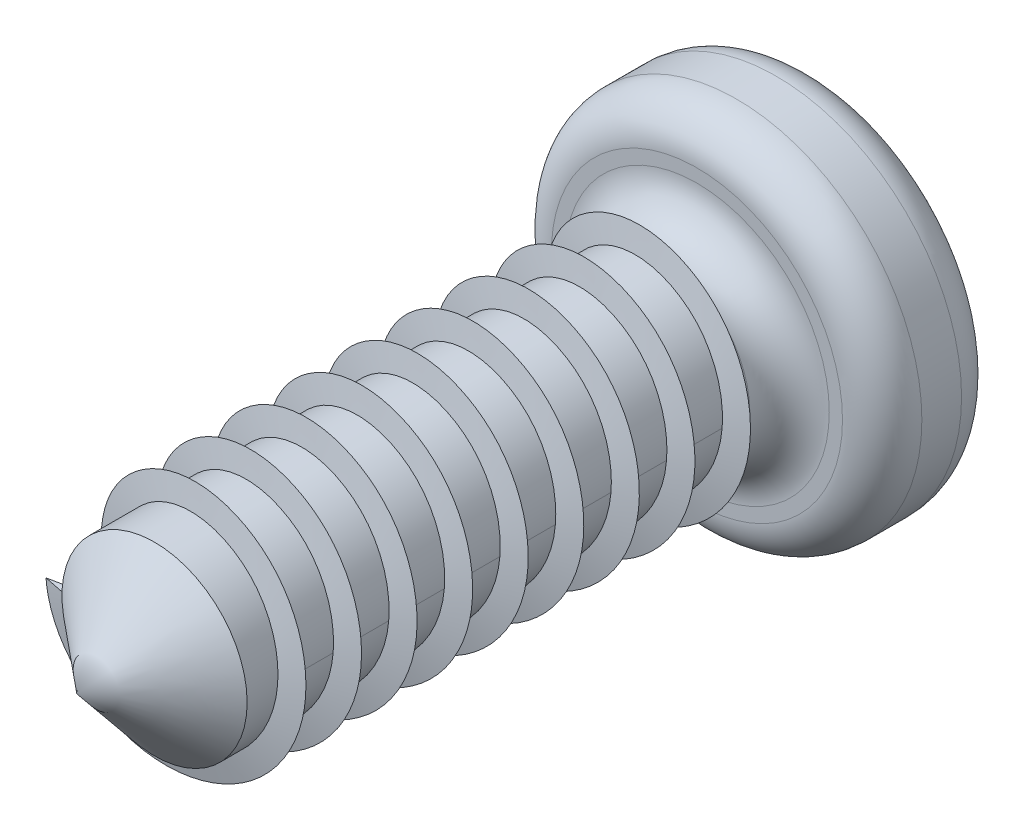
SolidWorks part; units mm, degrees
ref_plane "Front" through (0, 0, 0) normal (0, 0, 1) x (1, 0, 0)
ref_plane "Top" through (0, 0, 0) normal (0, 1, 0) x (1, 0, 0)
ref_plane "Right" through (0, 0, 0) normal (1, 0, 0) x (0, 0, -1)
sketch "Sketch1" plane through (0, 0, 0) normal (0, 0, 1) x (1, 0, 0)
  circle A0 centre (0, 0) radius 1.4
  dimension "D1" = 2.8
extrude "Boss-Extrude1" add sketch "Sketch1" along normal blind 5
sketch "Sketch2" plane through (0, 0, 5) normal (0, 0, 1) x (1, 0, 0)
  circle A0 centre (0, 0) radius 1.4 construction
  circle A1 centre (0, 0) radius 1.4
  circle A2 centre (0, 0) radius 0.7
  dimension "D1" = 0.7
extrude "Cut-Extrude1" cut sketch "Sketch2" against normal blind 4.1
sketch "Sketch3" plane through (0, 0, 5) normal (0, 0, 1) x (1, 0, 0)
  circle A0 centre (0, 0) radius 0.7
extrude "Boss-Extrude2" add sketch "Sketch3" along normal blind 0.6 draft 50
fillet "Fillet1" radius 0.3 2 edges at (1.4, 0, 0.9) (1.4, 0, 0)
fillet "Fillet2" radius 0.3 1 edges at (0.7, 0, 0.9)
sketch "Sketch4" plane through (0, 0, 0) normal (0, 0, -1) x (-1, 0, 0)
  line L0 (-0.15, -0.15) -> (-0.15, -0.9)
  line L1 (-0.15, 0.9) -> (0.15, 0.9)
  line L2 (-0.15, 0.9) -> (-0.15, 0.15)
  line L3 (-0.15, -0.9) -> (0.15, -0.9)
  line L4 (0.15, 0.9) -> (0.15, 0.15)
  line L5 (-0.15, 0.9) -> (0.15, -0.9) construction
  line L6 (-0.15, -0.9) -> (0.15, 0.9) construction
  line L7 (-0.9, -0.15) -> (-0.15, -0.15)
  line L8 (-0.9, -0.15) -> (-0.9, 0.15)
  line L9 (-0.9, 0.15) -> (-0.15, 0.15)
  line L10 (0.9, -0.15) -> (0.9, 0.15)
  line L11 (-0.9, -0.15) -> (0.9, 0.15) construction
  line L12 (-0.9, 0.15) -> (0.9, -0.15) construction
  line L13 (0.15, -0.15) -> (0.15, -0.9)
  line L14 (0.15, 0.15) -> (0.9, 0.15)
  line L15 (0.15, -0.15) -> (0.9, -0.15)
  point P0 (0, 0)
  point P6 (0, 0)
  dimension "D1" = 0.3
  dimension "D2" = 0.3
  dimension "D3" = 1.8
  dimension "D4" = 1.8
extrude "Cut-Extrude2" cut sketch "Sketch4" against normal blind 0.6
ref_plane "Plane1" through (0, 0, 1.2) normal (0, 0, 1) x (1, 0, 0)
sketch "Sketch5" plane through (0, 0, 1.2) normal (0, 0, 1) x (1, 0, 0)
  circle A0 centre (0, 0) radius 0.7
curve "Helix/Spiral1" pitch 0.42 height 3.78 radius 0.7 left hand yes centre (0, 0, 1.2) axis (0, 0, 1) start towards (1, 0, 0)
sketch "Sketch6" plane through (0, 0, 0) normal (0, 1, 0) x (1, 0, 0)
  line L0 (-50, -1.2) -> (50, -1.2) construction
  line L2 (-0.7, -1.2) -> (-0.7, -1.1283)
  line L5 (-0.7, -1.1283) -> (-0.8763, -1.1641)
  line L6 (-0.8763, -1.1641) -> (-0.7, -1.2)
  arc A0 (-0.7, -1.2) -> (-1, -0.9) centre (-1, -1.2) ccw construction
sweep "Sweep1" add profiles "Sketch6" path "Helix/Spiral1"
